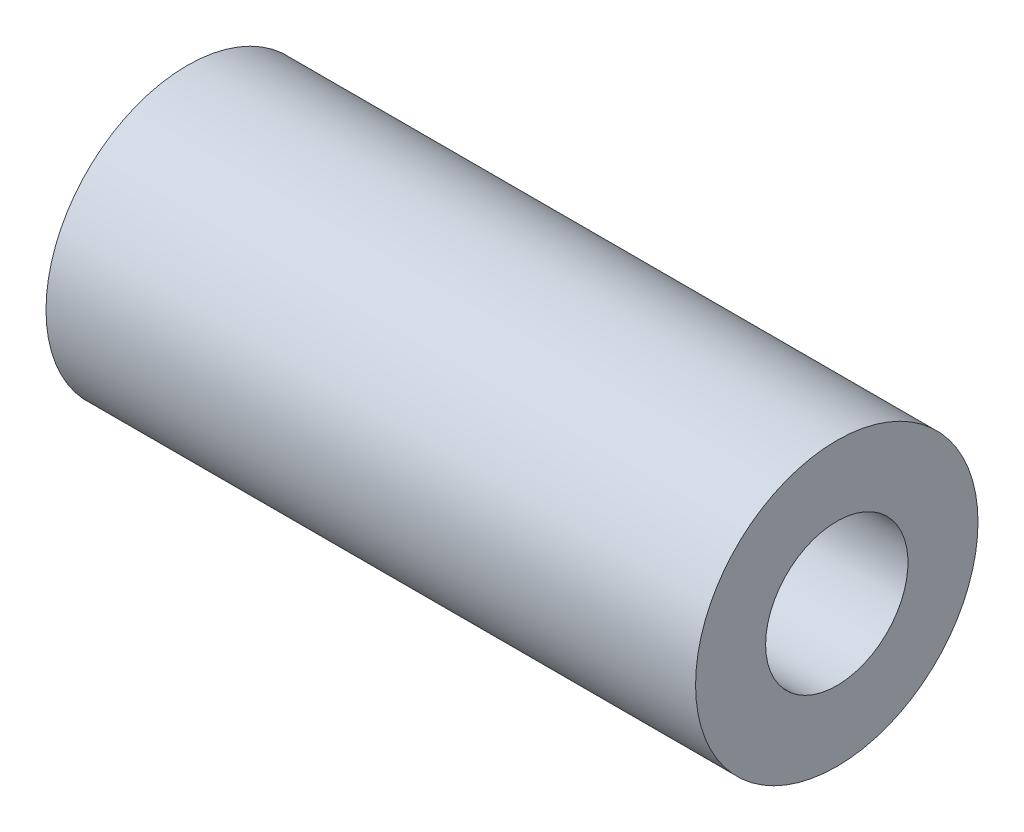
SolidWorks part; units mm, degrees
material "Nylon 101"
ref_plane "Front Plane" through (0, 0, 0) normal (0, 0, 1) x (1, 0, 0)
ref_plane "Top Plane" through (0, 0, 0) normal (0, 1, 0) x (1, 0, 0)
ref_plane "Right Plane" through (0, 0, 0) normal (1, 0, 0) x (0, 0, -1)
sketch "Sketch1" plane through (0, 0, 0) normal (1, 0, 0) x (0, 0, -1)
  circle A0 centre (0, 0) radius 3.2004
  circle A1 centre (0, 0) radius 6.35
  dimension "D1" = 12.7
  dimension "D2" = 6.4008
extrude "Boss-Extrude1" add sketch "Sketch1" along normal blind 29.21
